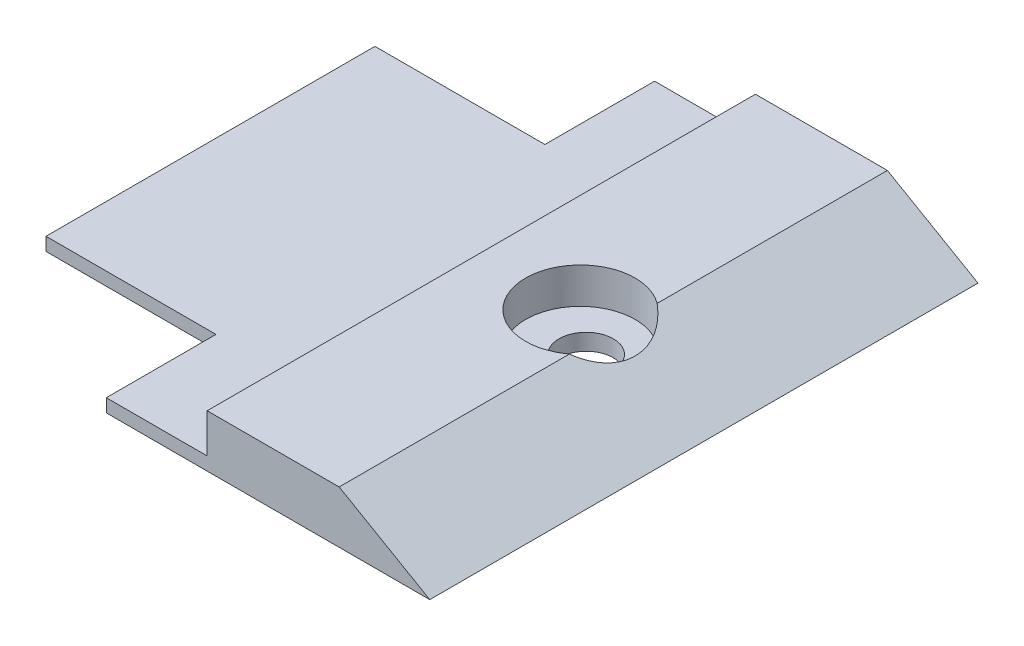
SolidWorks part; units mm, degrees
ref_plane "Alzado" through (0, 0, 0) normal (0, 0, 1) x (1, 0, 0)
ref_plane "Planta" through (0, 0, 0) normal (0, 1, 0) x (1, 0, 0)
ref_plane "Vista lateral" through (0, 0, 0) normal (1, 0, 0) x (0, 0, -1)
sketch "Croquis1" plane through (0, 0, 0) normal (0, 1, 0) x (1, 0, 0)
  line L0 (0, 0) -> (15.5, 0)
  line L1 (15.5, 0) -> (15.5, -10)
  line L2 (15.5, -10) -> (45, -10)
  line L3 (45, -10) -> (45, 40)
  line L4 (45, 40) -> (15.5, 40)
  line L5 (15.5, 40) -> (15.5, 30)
  line L6 (15.5, 30) -> (0, 30)
  line L7 (0, 30) -> (0, 0)
  point P9 (0, 15)
  point P10 (45, 15)
  dimension "D1" = 45
  dimension "D2" = 50
  dimension "D3" = 10
  dimension "D4" = 15.5
extrude "Saliente-Extruir1" add sketch "Croquis1" along normal blind 4.77
sketch "Croquis2" plane through (0, 0, 0) normal (0, 0, 1) x (1, 0, 0)
  line L0 (0, 0) -> (15.5, 0) construction
  line L1 (0, 4.77) -> (24.7, 4.77)
  line L2 (0, 4.77) -> (0, 1.2)
  line L3 (0, 1.2) -> (24.7, 1.2)
  line L4 (24.7, 4.77) -> (24.7, 1.2)
  dimension "D1" = 1.2
  dimension "D2" = 24.7
extrude "Cortar-Extruir1" cut sketch "Croquis2" against normal up to vertex (40 mm away) and the other way blind 10 up to point (15.5, 4.77, -40)
sketch "Croquis3" plane through (0, 0, 10) normal (0, 0, 1) x (1, 0, 0)
  line L0 (45, 0) -> (36.7381, 4.77)
  line L1 (24.7, 4.77) -> (45, 4.77) construction
  line L2 (36.7381, 4.77) -> (45, 4.77)
  line L3 (45, 4.77) -> (45, 0)
  line L4 (15.5, 0) -> (45, 0) construction
  dimension "D1" = 30
extrude "Cortar-Extruir2" cut sketch "Croquis3" against normal up to vertex (50 mm away) up to point (45, 4.77, -40)
sketch "Croquis4" plane through (0, 4.77, 0) normal (0, 1, 0) x (1, 0, 0)
  line L0 (0, 0) -> (0, 30) construction
  line L1 (32.5132, 13.25) -> (36.0132, 13.25) construction
  line L2 (32.5132, 13.25) -> (32.5132, 16.75) construction
  line L3 (32.5132, 16.75) -> (36.0132, 16.75) construction
  line L4 (36.0132, 13.25) -> (36.0132, 16.75) construction
  line L5 (32.5132, 13.25) -> (36.0132, 16.75) construction
  line L6 (32.5132, 16.75) -> (36.0132, 13.25) construction
  line L7 (36.7381, 40) -> (36.7381, -10) construction
  circle A0 centre (34.2632, 15) radius 2.4749
  point P8 (0, 15)
  dimension "D1" = 3.5
  dimension "D2" = 3.5
extrude "Cortar-Extruir3" cut sketch "Croquis4" against normal up to vertex (4.77 mm away) up to point (15.5, 0, 10)
sketch "Croquis5" plane through (0, 4.77, 0) normal (0, 1, 0) x (1, 0, 0)
  line L1 (45, -10) -> (45, 40) construction
  line L2 (30.7381, 19) -> (36.7381, 19) construction
  line L3 (30.7381, 19) -> (30.7381, 11) construction
  line L4 (30.7381, 11) -> (36.7381, 11) construction
  line L5 (36.7381, 19) -> (36.7381, 11) construction
  circle A2 centre (33.7381, 15) radius 5
  point P11 (45, 15)
  dimension "D3" = 8
  dimension "D4" = 6
extrude "Cortar-Extruir4" cut sketch "Croquis5" against normal blind 3.27
